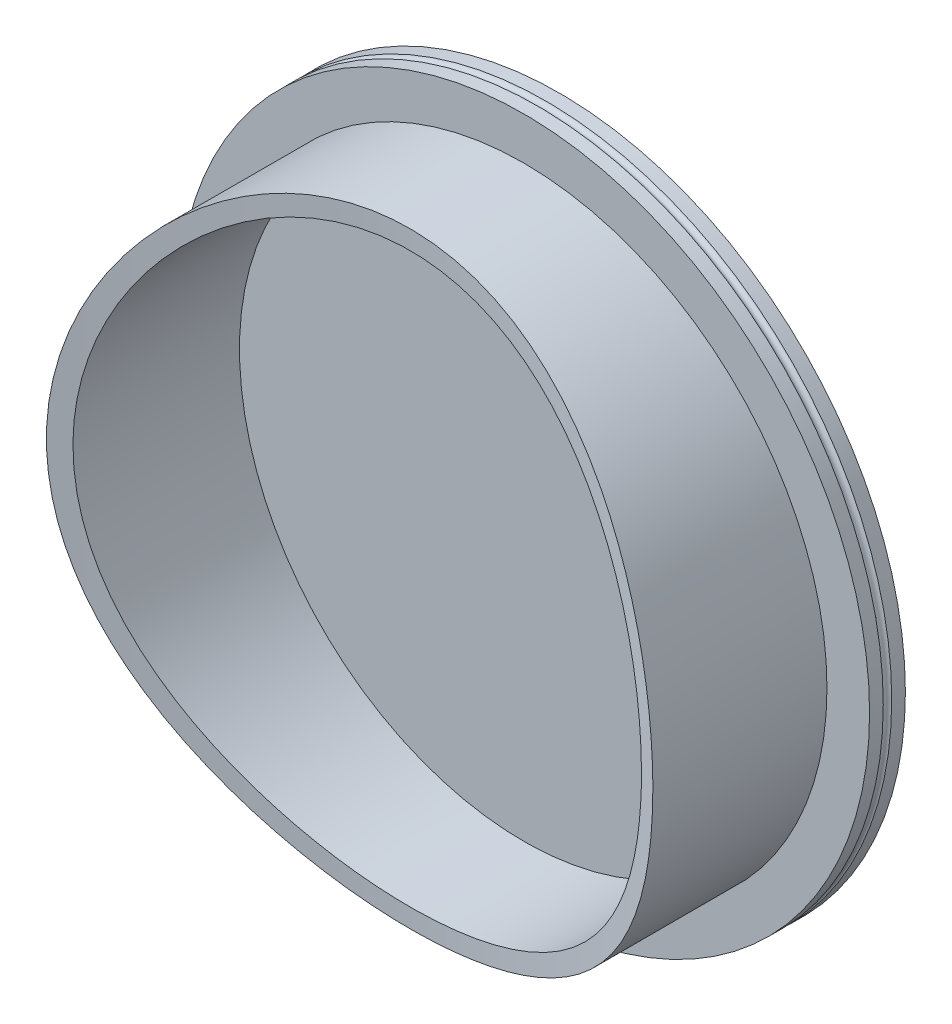
SolidWorks part; units mm, degrees
ref_plane "Front" through (0, 0, 0) normal (0, 0, 1) x (1, 0, 0)
ref_plane "Top" through (0, 0, 0) normal (0, 1, 0) x (1, 0, 0)
ref_plane "Right" through (0, 0, 0) normal (1, 0, 0) x (0, 0, -1)
ref_axis "Axis1" through (0, 0, -80.9) along (0, 0, 1)
sketch "Sketch1" plane through (0, 0, 0) normal (1, 0, 0) x (0, 0, -1)
  line L0 (-12, 0) -> (0, 0) construction
  line L4 (-4.5858, 115.875) -> (0, 115.875)
  line L6 (0, 113.375) -> (-2, 113.375)
  line L7 (-12, 101.6) -> (-12, 115.875)
  line L8 (-2, 113.375) -> (-2, 107.375)
  line L9 (-12, 115.875) -> (-7.4142, 115.875)
  line L10 (-2, 107.375) -> (0, 107.375)
  line L11 (0, 115.875) -> (0, 113.375)
  line L12 (0, 107.375) -> (0, 0)
  line L13 (0, 0) -> (-12, 0)
  line L14 (-12, 101.6) -> (-75.5, 101.6)
  line L15 (-75.5, 101.6) -> (-75.5, 95.25)
  line L16 (-75.5, 95.25) -> (-12, 95.25)
  line L17 (-12, 95.25) -> (-12, 0)
  arc A0 (-7.4142, 115.875) -> (-4.5858, 115.875) centre (-6, 116.375) ccw
  dimension "D6" = 3
  dimension "D9" = 1
  dimension "D2" = 63.5
  dimension "D4" = 231.75
  dimension "D5" = 12
  dimension "D8" = 6.35
  dimension "D10" = 214.75
  dimension "D11" = 6
  dimension "D12" = 2
  dimension "D13" = 95.25
revolve "Base-Revolve" add sketch "Sketch1" angle 360 about L0
sketch "External extrusion" plane through (0, 0, 0) normal (0, 1, 0) x (1, 0, 0)
  line L0 (0, -170.6297) -> (0, 116.3238) construction
  line L3 (-115.875, -12) -> (115.875, -12) construction
  circle A0 centre (0, -315.0218) radius 264.93
  dimension "D1" = 303.0218
  dimension "D2" = 529.86
extrude "Cut-Extrude1" cut sketch "External extrusion" against normal through all and the other way through all
